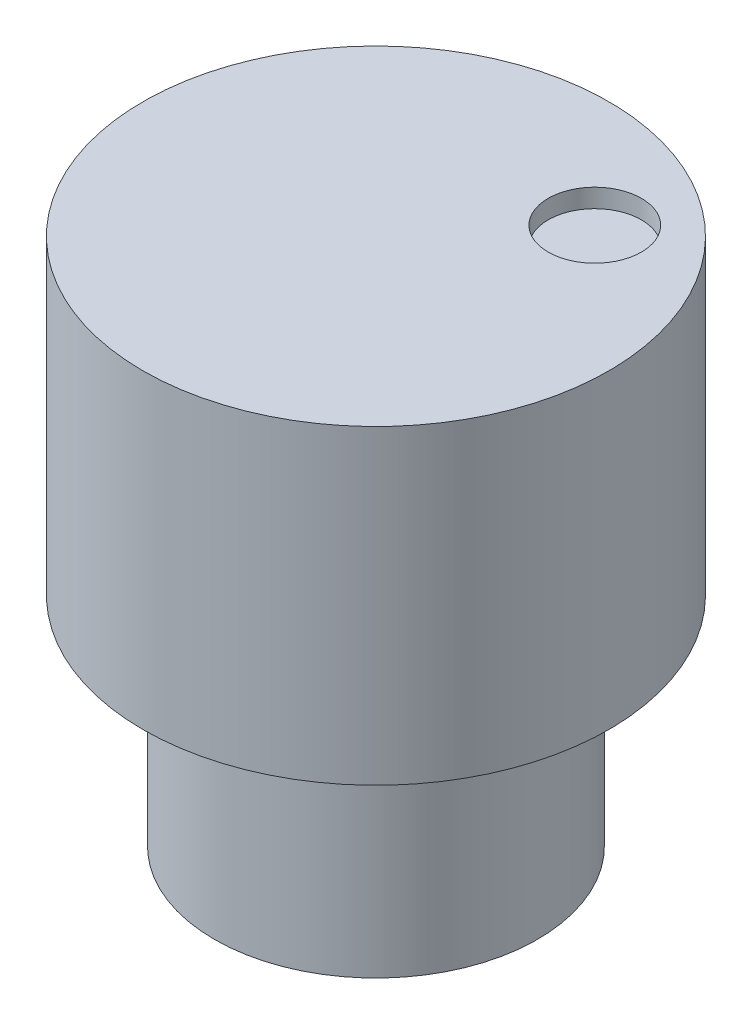
SolidWorks part; units mm, degrees
ref_plane "Front Plane" through (0, 0, 0) normal (0, 0, 1) x (1, 0, 0)
ref_plane "Top Plane" through (0, 0, 0) normal (0, 1, 0) x (1, 0, 0)
ref_plane "Right Plane" through (0, 0, 0) normal (1, 0, 0) x (0, 0, -1)
sketch "Sketch1" plane through (0, 0, 0) normal (0, 1, 0) x (1, 0, 0)
  circle A0 centre (0, 0) radius 3.2
  circle A1 centre (0, 0) radius 5.2
  dimension "D1" = 6.4
  dimension "D2" = 2
extrude "Boss-Extrude1" add sketch "Sketch1" along normal blind 7
sketch "Sketch2" plane through (0, 7, 0) normal (0, 1, 0) x (1, 0, 0)
  circle A0 centre (0, 0) radius 7.5
  dimension "D1" = 15
extrude "Boss-Extrude2" add sketch "Sketch2" along normal blind 10
sketch "Sketch4" plane through (0, 7, 0) normal (0, -1, 0) x (1, 0, 0)
  line L0 (-2.6458, -1.8) -> (2.6458, -1.8)
  circle A1 centre (0, 0) radius 3.2
  circle A2 centre (0, 0) radius 3.2
  circle A3 centre (0, 0) radius 3.2 construction
  point P7 (0, 3.2)
  circle M5 centre (0, 0) radius 3.2
  dimension "D2" = 5
  dimension "D1" = 0
extrude "Boss-Extrude4" add sketch "Sketch4" along normal blind 5 contours L0 M5 region at (0, 7, -2.372)
sketch "Sketch5" plane through (0, 17, 0) normal (0, 1, 0) x (1, 0, 0)
  line L0 (-2.6458, 1.8) -> (2.6458, 1.8) construction
  line L1 (-2.6458, 1.8) -> (2.6458, 1.8) construction
  line L2 (0, 1.8) -> (0, -7.5) construction
  line L3 (3.2139, 3.8302) -> (0, 0) construction
  circle A0 centre (3.2139, 3.8302) radius 1.5
  circle A1 centre (0, 0) radius 7.5 construction
  dimension "D3" = 3
  dimension "D1" = 220
  dimension "D2" = 5
extrude "Cut-Extrude1" cut sketch "Sketch5" against normal blind 0.6
